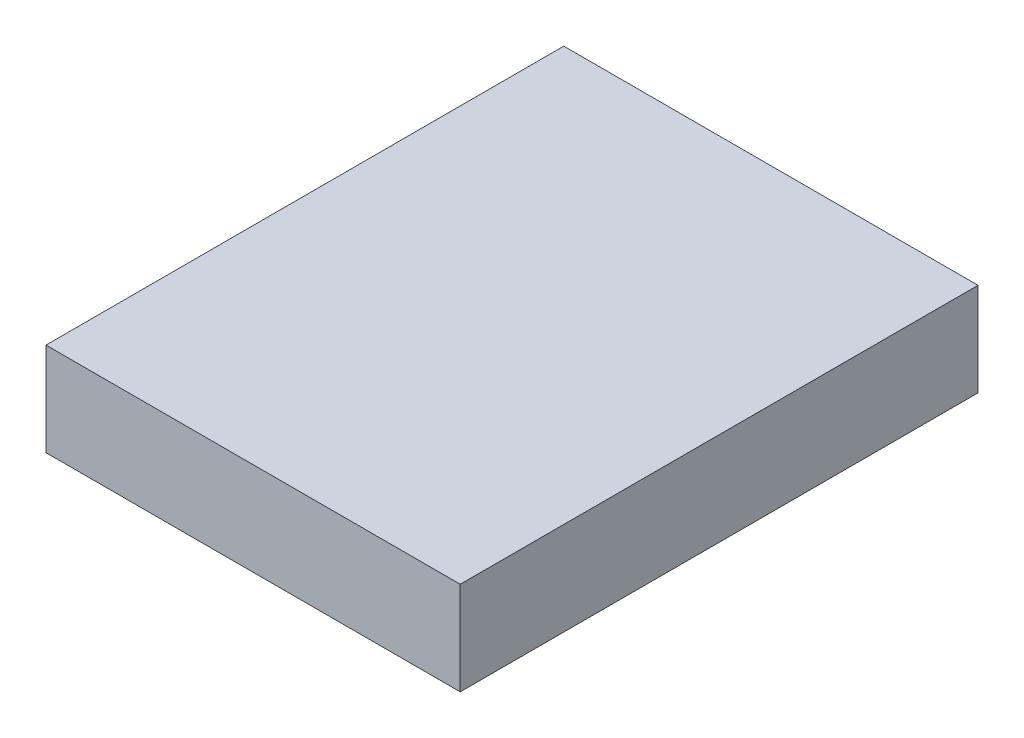
SolidWorks part; units mm, degrees
ref_plane "Front Plane" through (0, 0, 0) normal (0, 0, 1) x (1, 0, 0)
ref_plane "Top Plane" through (0, 0, 0) normal (0, 1, 0) x (1, 0, 0)
ref_plane "Right Plane" through (0, 0, 0) normal (1, 0, 0) x (0, 0, -1)
ref_axis "X-Axis" through (-88.99, 0, 0) along (1, 0, 0)
ref_axis "Y-Axis" through (0, 55, 0) along (0, -1, 0)
ref_axis "Z-Axis" through (0, 0, -88.99) along (0, 0, 1)
sketch "Sketch1" plane through (0, 0, 0) normal (0, 1, 0) x (1, 0, 0)
  line L1 (-4, -5) -> (4, -5)
  line L2 (-4, -5) -> (-4, 5)
  line L3 (-4, 5) -> (4, 5)
  line L4 (4, -5) -> (4, 5)
  line L5 (-4, -5) -> (4, 5) construction
  line L6 (-4, 5) -> (4, -5) construction
  point P0 (0, 0)
  dimension "D1" = 8
  dimension "D2" = 10
extrude "Boss-Extrude1" add sketch "Sketch1" along normal blind 1.8
